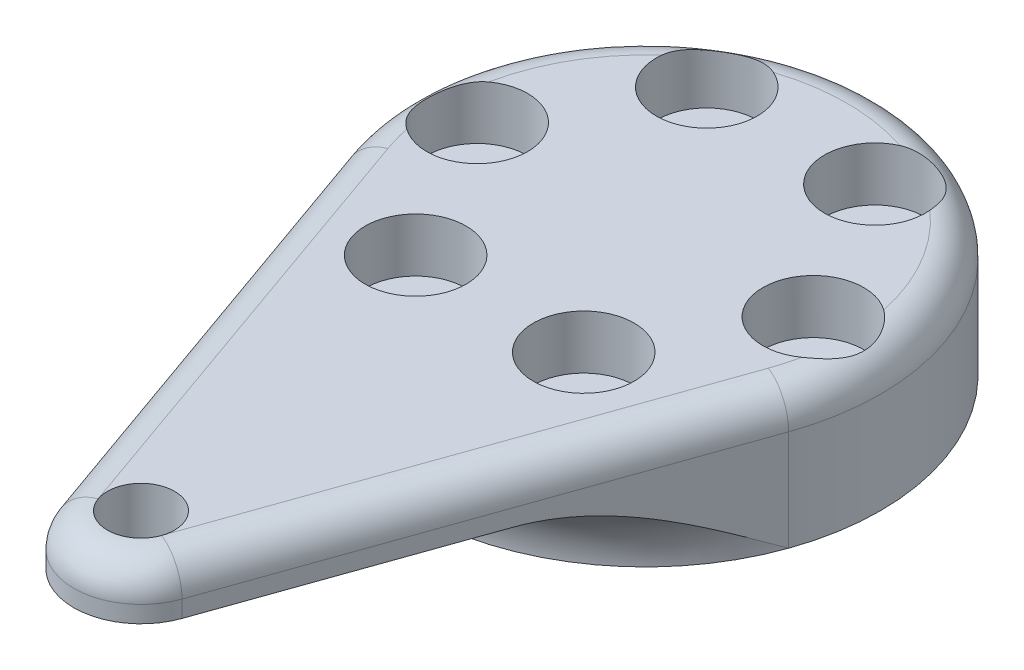
SolidWorks part; units mm, degrees
material "1060 合金"
ref_plane "前视基准面" through (0, 0, 0) normal (0, 0, 1) x (1, 0, 0)
ref_plane "上视基准面" through (0, 0, 0) normal (0, 1, 0) x (1, 0, 0)
ref_plane "右视基准面" through (0, 0, 0) normal (1, 0, 0) x (0, 0, -1)
sketch "Sketch1" plane through (0, 0, 0) normal (0, 1, 0) x (1, 0, 0)
  circle A0 centre (0, 0) radius 14
  circle A1 centre (0, 0) radius 10 construction
  circle A2 centre (-10, 0) radius 1.2
  circle A3 centre (-5, 8.6603) radius 1.2
  circle A4 centre (5, 8.6603) radius 1.2
  circle A5 centre (10, 0) radius 1.2
  circle A6 centre (5, -8.6603) radius 1.2
  circle A7 centre (-5, -8.6603) radius 1.2
  point P18 (0, 0)
  dimension "D1" = 6
extrude "Boss-Extrude1" add sketch "Sketch1" along normal blind 5 contours A0 A7 A1 A2 A3 A4 A5 A6 | A7 A1 A6 A5 A4 A3 A2 region at (0, 0, 0)
sketch "Sketch2" plane through (0, 5, 0) normal (0, 1, 0) x (1, 0, 0)
  line L0 (-3.7712, -31.3333) -> (-13.1993, -4.6667)
  line L1 (3.7712, -31.3333) -> (13.1993, -4.6667)
  circle A0 centre (-10, 0) radius 1.2
  circle A1 centre (0, 0) radius 14
  circle A2 centre (0, 0) radius 14
  circle A3 centre (-5, 8.6603) radius 1.2
  circle A4 centre (5, 8.6603) radius 1.2
  circle A5 centre (10, 0) radius 1.2
  circle A6 centre (5, -8.6603) radius 1.2
  circle A7 centre (-5, -8.6603) radius 1.2
  circle A8 centre (0, 0) radius 14
  circle A9 centre (0, -30) radius 4
  circle A10 centre (0, -30) radius 2
  point P18 (0, 0)
  circle M3 centre (-5, -8.6603) radius 1.2
  circle M4 centre (-10, 0) radius 1.2
  circle M5 centre (-5, 8.6603) radius 1.2
  circle M6 centre (5, 8.6603) radius 1.2
  circle M7 centre (10, 0) radius 1.2
  circle M8 centre (5, -8.6603) radius 1.2
  circle M9 centre (0, 0) radius 14
  dimension "D1" = 0
  dimension "D2" = 6
extrude "Boss-Extrude2" add sketch "Sketch2" along normal blind 3 contours A9 L1 L0 M9 | M9 M4 M6 M8 M7 M5 M3 | A9 A10 region at (0, 5, 18.8099) region at (-0.6573, 5, 26.1691) region at (0, 5, 0)
fillet "Fillet1" radius 5 1 edges at (0, 5, 14)
sketch "Sketch3" plane through (0, 8, 0) normal (0, 1, 0) x (1, 0, 0)
  circle A0 centre (-10, 0) radius 3
  circle A1 centre (-5, 8.6603) radius 3
  circle A2 centre (5, 8.6603) radius 3
  circle A3 centre (10, 0) radius 3
  circle A4 centre (5, -8.6603) radius 3
  circle A5 centre (-5, -8.6603) radius 3
  point P16 (0, 0)
  dimension "D1" = 6
extrude "Cut-Extrude1" cut sketch "Sketch3" against normal blind 3.2
fillet "Fillet2" radius 2 4 edges at (0, 8, 34) (0, 8, -14) (8.4853, 8, 18) (-8.4853, 8, 18)
